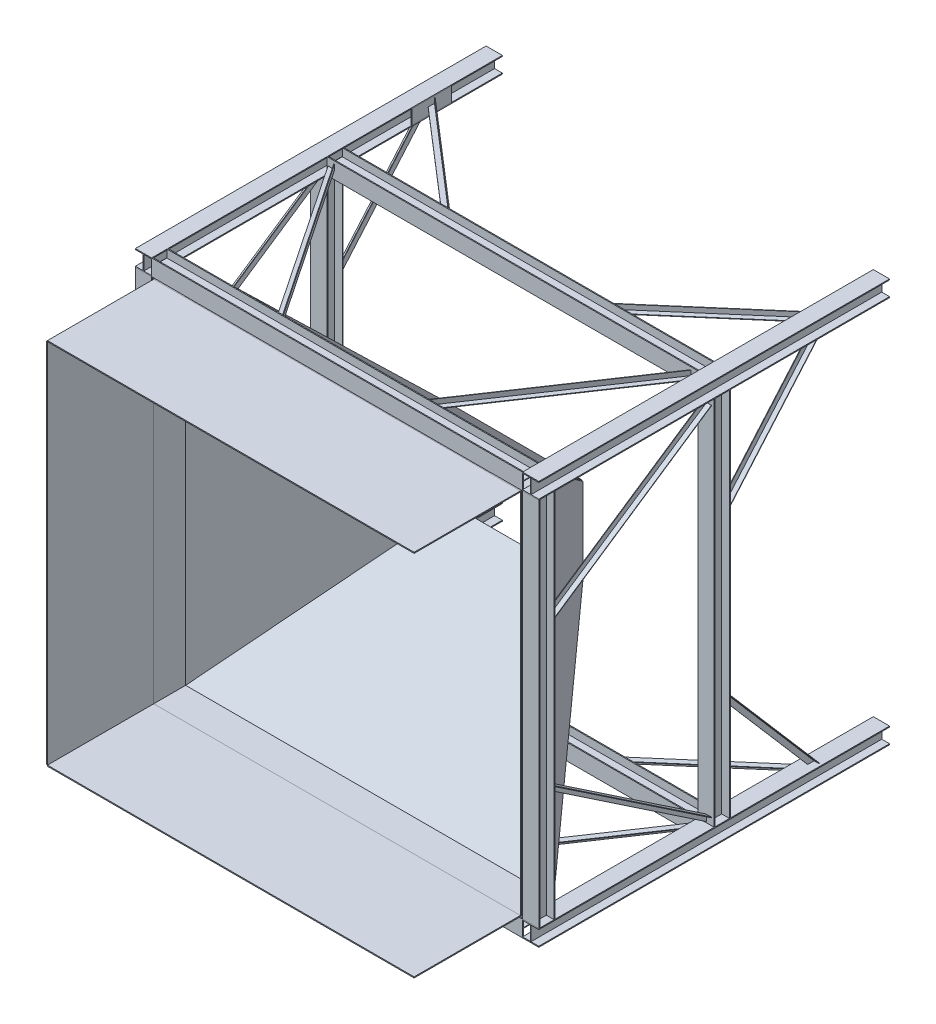
SolidWorks part; units mm, degrees
other "DetailItem1"
other "DetailItem2"
other "DetailItem3"
other "DetailItem4"
other "DetailItem5"
other "DetailItem6"
other "DetailItem7"
other "DetailItem8"
other "DetailItem9"
other "DetailItem10"
other "DetailItem11"
other "DetailItem12"
other "DetailItem13"
other "DetailItem14"
other "DetailItem15"
other "DetailItem16"
other "DetailItem17"
other "DetailItem18"
other "DetailItem19"
other "DetailItem20"
other "DetailItem21"
other "DetailItem22"
other "DetailItem23"
other "DetailItem24"
other "DetailItem25"
other "DetailItem26"
other "DetailItem27"
other "DetailItem28"
other "DetailItem29"
other "DetailItem30"
other "DetailItem31"
other "DetailItem32"
other "DetailItem33"
other "DetailItem34"
other "DetailItem35"
other "DetailItem36"
other "DetailItem37"
other "DetailItem38"
other "DetailItem39"
other "DetailItem40"
other "DetailItem41"
other "DetailItem42"
other "DetailItem43"
other "DetailItem44"
other "DetailItem45"
other "DetailItem46"
other "DetailItem47"
other "DetailItem48"
other "DetailItem49"
other "DetailItem50"
other "DetailItem51"
other "DetailItem52"
other "DetailItem53"
other "DetailItem54"
other "DetailItem55"
other "DetailItem56"
other "DetailItem57"
other "DetailItem58"
other "DetailItem59"
other "DetailItem60"
other "DetailItem61"
other "DetailItem62"
other "DetailItem63"
other "DetailItem64"
other "DetailItem65"
other "DetailItem66"
other "DetailItem67"
other "DetailItem68"
other "DetailItem69"
other "DetailItem70"
other "DetailItem71"
other "DetailItem72"
other "DetailItem73"
other "Carpeta de soldadura"
other "Cordón de soldadura1"
other "Soldadura Viga H carga 1650 B"
other "Soldadura Viga H carga 3300 A"
other "Soldadura Viga H carga 3300 B"
other "Soldadura asiento a tolva carga"
other "Soldadura asiento a bastidor carga"
other "Soldadura Viga H fondo 1650 A"
other "Soldadura Viga H fondo 1650 B"
other "Soldadura Viga H fondo 3300 A"
other "Soldadura Viga H fondo 3300 B"
other "Soldadura asiento a tolva fondo"
other "Soldadura asiento a bastidor fondo"
other "Soldadura Viga H izquierda 1650 A"
other "Soldadura Viga H izquierda 1650 B"
other "Soldadura Viga H izquierda 3300 A"
other "Soldadura Viga H izquierda 3300 B"
other "Soldadura asiento a tolva izquierda"
other "Soldadura asiento a bastidor izquierda"
other "Soldadura Viga H derecha 1650 A"
other "Soldadura Viga H derecha 1650 B"
other "Soldadura Viga H derecha 3300 A"
other "Soldadura Viga H derecha 3300 B"
other "Soldadura asiento a tolva derecha"
other "Soldadura asiento a bastidor derecha"
other "Soldadura Angular superior carga A inferior"
other "Soldadura Angular superior carga A superior"
other "Soldadura Angular inferior carga A inferior"
other "Soldadura Angular inferior carga A superior"
other "Soldadura Angular superior carga B inferior"
other "Soldadura Angular superior carga B superior"
other "Soldadura Angular inferior carga B inferior"
other "Soldadura Angular inferior carga B superior"
other "Soldadura Angular superior fondo A inferior"
other "Soldadura Angular superior fondo A superior"
other "Soldadura Angular inferior fondo A inferior"
other "Soldadura Angular inferior fondo A superior"
other "Soldadura Angular superior fondo B inferior"
other "Soldadura Angular superior fondo B superior"
other "Soldadura Angular inferior fondo B inferior"
other "Soldadura Angular inferior fondo B superior"
other "Soldadura Angular superior izquierda A inferior"
other "Soldadura Angular superior izquierda A superior"
other "Soldadura Angular inferior izquierda A inferior"
other "Soldadura Angular inferior izquierda A superior"
other "Soldadura Angular superior izquierda B inferior"
other "Soldadura Angular superior izquierda B superior"
other "Soldadura Angular inferior izquierda B inferior"
other "Soldadura Angular inferior izquierda B superior"
other "Soldadura Angular superior derecha A inferior"
other "Soldadura Angular superior derecha A superior"
other "Soldadura Angular inferior derecha A inferior"
other "Soldadura Angular inferior derecha A superior"
other "Soldadura Angular superior derecha B inferior"
other "Soldadura Angular superior derecha B superior"
other "Soldadura Angular inferior derecha B inferior"
other "Soldadura Angular inferior derecha B superior"
other "Soldadura alerón a collar lateral Y negativo"
other "Soldadura esquina del collar lateral Y negativo"
other "Soldadura quiebre del embudo lateral Y negativo"
other "Soldadura arista inclinada lateral Y negativo"
other "Soldadura esquina del collar carga"
other "Soldadura quiebre del embudo carga"
other "Soldadura arista inclinada carga"
other "Soldadura alerón a collar lateral Y positivo"
other "Soldadura esquina del collar lateral Y positivo"
other "Soldadura quiebre del embudo lateral Y positivo"
other "Soldadura arista inclinada lateral Y positivo"
other "Soldadura alerón a collar fondo X negativo"
other "Soldadura esquina del collar fondo X negativo"
other "Soldadura quiebre del embudo fondo X negativo"
other "Soldadura arista inclinada fondo X negativo"
other "Soldadura esquina alerones fondo Y positivo"
other "Soldadura esquina alerones fondo Y negativo"
material "ASTM A36 Steel"
ref_plane "Front Plane" through (0, 0, 0) normal (0, 0, 1) x (1, 0, 0)
ref_plane "Top Plane" through (0, 0, 0) normal (0, 1, 0) x (1, 0, 0)
ref_plane "Right Plane" through (0, 0, 0) normal (1, 0, 0) x (0, 0, -1)
sketch3d "Referencias 1"
  point P0 (0, 0, 0)
  point P1 (0, -190, 0)
  point P2 (200, 0, 0)
ref_plane "Plano de perfil 1 estructura" through (0, 0, 0) normal (0, 0, 1) x (1, 0, 0)
sketch "Contorno Columna H 1" plane through (0, 0, 0) normal (0, 0, 1) x (1, 0, 0)
  line L0 (-1898, -1898) -> (-1745, -1898)
  line L1 (-1745, -1898) -> (-1745, -1889)
  line L2 (-1745, -1889) -> (-1818.25, -1889)
  line L3 (-1818.25, -1889) -> (-1818.25, -1754)
  line L4 (-1818.25, -1754) -> (-1745, -1754)
  line L5 (-1745, -1754) -> (-1745, -1745)
  line L6 (-1745, -1745) -> (-1898, -1745)
  line L7 (-1898, -1745) -> (-1898, -1754)
  line L8 (-1898, -1754) -> (-1824.75, -1754)
  line L9 (-1824.75, -1754) -> (-1824.75, -1889)
  line L10 (-1824.75, -1889) -> (-1898, -1889)
  line L11 (-1898, -1889) -> (-1898, -1898)
extrude "Columna H 1" add sketch "Contorno Columna H 1" along normal blind 3300 separate body
sketch "Contorno Columna H 2" plane through (0, 0, 0) normal (0, 0, 1) x (1, 0, 0)
  line L0 (-1898, 1745) -> (-1745, 1745)
  line L1 (-1745, 1745) -> (-1745, 1754)
  line L2 (-1745, 1754) -> (-1818.25, 1754)
  line L3 (-1818.25, 1754) -> (-1818.25, 1889)
  line L4 (-1818.25, 1889) -> (-1745, 1889)
  line L5 (-1745, 1889) -> (-1745, 1898)
  line L6 (-1745, 1898) -> (-1898, 1898)
  line L7 (-1898, 1898) -> (-1898, 1889)
  line L8 (-1898, 1889) -> (-1824.75, 1889)
  line L9 (-1824.75, 1889) -> (-1824.75, 1754)
  line L10 (-1824.75, 1754) -> (-1898, 1754)
  line L11 (-1898, 1754) -> (-1898, 1745)
extrude "Columna H 2" add sketch "Contorno Columna H 2" along normal blind 3300 separate body
sketch "Contorno Columna H 3" plane through (0, 0, 0) normal (0, 0, 1) x (1, 0, 0)
  line L0 (1745, -1898) -> (1898, -1898)
  line L1 (1898, -1898) -> (1898, -1889)
  line L2 (1898, -1889) -> (1824.75, -1889)
  line L3 (1824.75, -1889) -> (1824.75, -1754)
  line L4 (1824.75, -1754) -> (1898, -1754)
  line L5 (1898, -1754) -> (1898, -1745)
  line L6 (1898, -1745) -> (1745, -1745)
  line L7 (1745, -1745) -> (1745, -1754)
  line L8 (1745, -1754) -> (1818.25, -1754)
  line L9 (1818.25, -1754) -> (1818.25, -1889)
  line L10 (1818.25, -1889) -> (1745, -1889)
  line L11 (1745, -1889) -> (1745, -1898)
extrude "Columna H 3" add sketch "Contorno Columna H 3" along normal blind 3300 separate body
sketch "Contorno Columna H 4" plane through (0, 0, 0) normal (0, 0, 1) x (1, 0, 0)
  line L0 (1745, 1745) -> (1898, 1745)
  line L1 (1898, 1745) -> (1898, 1754)
  line L2 (1898, 1754) -> (1824.75, 1754)
  line L3 (1824.75, 1754) -> (1824.75, 1889)
  line L4 (1824.75, 1889) -> (1898, 1889)
  line L5 (1898, 1889) -> (1898, 1898)
  line L6 (1898, 1898) -> (1745, 1898)
  line L7 (1745, 1898) -> (1745, 1889)
  line L8 (1745, 1889) -> (1818.25, 1889)
  line L9 (1818.25, 1889) -> (1818.25, 1754)
  line L10 (1818.25, 1754) -> (1745, 1754)
  line L11 (1745, 1754) -> (1745, 1745)
extrude "Columna H 4" add sketch "Contorno Columna H 4" along normal blind 3300 separate body
sketch3d "Referencias 2"
  point P0 (-1745, 0, 0)
  point P1 (-1745, 190, 0)
  point P2 (-1745, 0, 200)
ref_plane "Plano de perfil 2 estructura" through (-1745, 0, 0) normal (1, 0, 0) x (0, 0, -1)
sketch "Contorno Viga H carga 1650" plane through (-1745, 0, 0) normal (1, 0, 0) x (0, 0, -1)
  line L0 (-1497, -1745) -> (-1497, -1898)
  line L1 (-1497, -1898) -> (-1506, -1898)
  line L2 (-1506, -1898) -> (-1506, -1824.75)
  line L3 (-1506, -1824.75) -> (-1641, -1824.75)
  line L4 (-1641, -1824.75) -> (-1641, -1898)
  line L5 (-1641, -1898) -> (-1650, -1898)
  line L6 (-1650, -1898) -> (-1650, -1745)
  line L7 (-1650, -1745) -> (-1641, -1745)
  line L8 (-1641, -1745) -> (-1641, -1818.25)
  line L9 (-1641, -1818.25) -> (-1506, -1818.25)
  line L10 (-1506, -1818.25) -> (-1506, -1745)
  line L11 (-1506, -1745) -> (-1497, -1745)
extrude "Viga H carga 1650" add sketch "Contorno Viga H carga 1650" along normal blind 3490 separate body
sketch "Contorno Viga H carga 3300" plane through (-1745, 0, 0) normal (1, 0, 0) x (0, 0, -1)
  line L0 (-3147, -1745) -> (-3147, -1898)
  line L1 (-3147, -1898) -> (-3156, -1898)
  line L2 (-3156, -1898) -> (-3156, -1824.75)
  line L3 (-3156, -1824.75) -> (-3291, -1824.75)
  line L4 (-3291, -1824.75) -> (-3291, -1898)
  line L5 (-3291, -1898) -> (-3300, -1898)
  line L6 (-3300, -1898) -> (-3300, -1745)
  line L7 (-3300, -1745) -> (-3291, -1745)
  line L8 (-3291, -1745) -> (-3291, -1818.25)
  line L9 (-3291, -1818.25) -> (-3156, -1818.25)
  line L10 (-3156, -1818.25) -> (-3156, -1745)
  line L11 (-3156, -1745) -> (-3147, -1745)
extrude "Viga H carga 3300" add sketch "Contorno Viga H carga 3300" along normal blind 3490 separate body
sketch "Contorno Cierre columna carga A" plane through (-1745, 0, 0) normal (1, 0, 0) x (0, 0, -1)
  line L0 (-480, -1754) -> (-480, -1889)
  line L1 (-480, -1889) -> (-850, -1889)
  line L2 (-850, -1889) -> (-850, -1754)
  line L3 (-850, -1754) -> (-480, -1754)
extrude "Cierre columna carga A" add sketch "Contorno Cierre columna carga A" against normal blind 8 separate body
sketch3d "Referencias 3"
  point P0 (0, -1821.5, 0)
  point P1 (-190, -1821.5, 0)
  point P2 (0, -1821.5, 200)
ref_plane "Plano de perfil 3 estructura" through (0, -1821.5, 0) normal (0, 1, 0) x (1, 0, 0)
sketch "Contorno Ala plana Angular superior carga A" plane through (0, -1821.5, 0) normal (0, 1, 0) x (1, 0, 0)
  line L0 (-1674.8701, -1650) -> (-1735.1299, -1650)
  line L1 (-1735.1299, -1650) -> (-728.1299, -3147)
  line L2 (-728.1299, -3147) -> (-667.8701, -3147)
  line L3 (-667.8701, -3147) -> (-1674.8701, -1650)
extrude "Ala plana Angular superior carga A" add sketch "Contorno Ala plana Angular superior carga A" against normal blind 5 separate body
sketch3d "Referencias 4"
  point P0 (0, -1826.5, 0)
  point P1 (-190, -1826.5, 0)
  point P2 (0, -1826.5, 200)
ref_plane "Plano de perfil 4 estructura" through (0, -1826.5, 0) normal (0, 1, 0) x (1, 0, 0)
sketch "Contorno Retorno Angular superior carga A" plane through (0, -1826.5, 0) normal (0, 1, 0) x (1, 0, 0)
  line L0 (-1674.8701, -1650) -> (-1680.8961, -1650)
  line L1 (-1680.8961, -1650) -> (-673.8961, -3147)
  line L2 (-673.8961, -3147) -> (-667.8701, -3147)
  line L3 (-667.8701, -3147) -> (-1674.8701, -1650)
extrude "Retorno Angular superior carga A" add sketch "Contorno Retorno Angular superior carga A" against normal blind 45 separate body
combine bodies "Angular superior carga A" operation type add bodies to combine 108 109
sketch "Contorno Ala plana Angular inferior carga A" plane through (0, -1821.5, 0) normal (0, 1, 0) x (1, 0, 0)
  line L0 (-1745, -631.991) -> (-1745, -698.009)
  line L1 (-1745, -698.009) -> (-818.2856, -1497)
  line L2 (-818.2856, -1497) -> (-741.7144, -1497)
  line L3 (-741.7144, -1497) -> (-1745, -631.991)
extrude "Ala plana Angular inferior carga A" add sketch "Contorno Ala plana Angular inferior carga A" against normal blind 5 separate body
sketch "Contorno Retorno Angular inferior carga A" plane through (0, -1826.5, 0) normal (0, 1, 0) x (1, 0, 0)
  line L0 (-1745, -631.991) -> (-1745, -638.5928)
  line L1 (-1745, -638.5928) -> (-749.3715, -1497)
  line L2 (-749.3715, -1497) -> (-741.7144, -1497)
  line L3 (-741.7144, -1497) -> (-1745, -631.991)
extrude "Retorno Angular inferior carga A" add sketch "Contorno Retorno Angular inferior carga A" against normal blind 45 separate body
combine bodies "Angular inferior carga A" operation type add bodies to combine 111 112
sketch3d "Referencias 5"
  point P0 (1745, 0, 0)
  point P1 (1745, 190, 0)
  point P2 (1745, 0, 200)
ref_plane "Plano de perfil 5 estructura" through (1745, 0, 0) normal (1, 0, 0) x (0, 0, -1)
sketch "Contorno Cierre columna carga B" plane through (1745, 0, 0) normal (1, 0, 0) x (0, 0, -1)
  line L0 (-480, -1754) -> (-480, -1889)
  line L1 (-480, -1889) -> (-850, -1889)
  line L2 (-850, -1889) -> (-850, -1754)
  line L3 (-850, -1754) -> (-480, -1754)
extrude "Cierre columna carga B" add sketch "Contorno Cierre columna carga B" along normal blind 8 separate body
sketch "Contorno Ala plana Angular superior carga B" plane through (0, -1821.5, 0) normal (0, 1, 0) x (1, 0, 0)
  line L0 (1674.8701, -1650) -> (1735.1299, -1650)
  line L1 (1735.1299, -1650) -> (728.1299, -3147)
  line L2 (728.1299, -3147) -> (667.8701, -3147)
  line L3 (667.8701, -3147) -> (1674.8701, -1650)
extrude "Ala plana Angular superior carga B" add sketch "Contorno Ala plana Angular superior carga B" against normal blind 5 separate body
sketch "Contorno Retorno Angular superior carga B" plane through (0, -1826.5, 0) normal (0, 1, 0) x (1, 0, 0)
  line L0 (1674.8701, -1650) -> (1680.8961, -1650)
  line L1 (1680.8961, -1650) -> (673.8961, -3147)
  line L2 (673.8961, -3147) -> (667.8701, -3147)
  line L3 (667.8701, -3147) -> (1674.8701, -1650)
extrude "Retorno Angular superior carga B" add sketch "Contorno Retorno Angular superior carga B" against normal blind 45 separate body
combine bodies "Angular superior carga B" operation type add bodies to combine 115 116
sketch "Contorno Ala plana Angular inferior carga B" plane through (0, -1821.5, 0) normal (0, 1, 0) x (1, 0, 0)
  line L0 (1745, -631.991) -> (1745, -698.009)
  line L1 (1745, -698.009) -> (818.2856, -1497)
  line L2 (818.2856, -1497) -> (741.7144, -1497)
  line L3 (741.7144, -1497) -> (1745, -631.991)
extrude "Ala plana Angular inferior carga B" add sketch "Contorno Ala plana Angular inferior carga B" against normal blind 5 separate body
sketch "Contorno Retorno Angular inferior carga B" plane through (0, -1826.5, 0) normal (0, 1, 0) x (1, 0, 0)
  line L0 (1745, -631.991) -> (1745, -638.5928)
  line L1 (1745, -638.5928) -> (749.3715, -1497)
  line L2 (749.3715, -1497) -> (741.7144, -1497)
  line L3 (741.7144, -1497) -> (1745, -631.991)
extrude "Retorno Angular inferior carga B" add sketch "Contorno Retorno Angular inferior carga B" against normal blind 45 separate body
combine bodies "Angular inferior carga B" operation type add bodies to combine 118 119
sketch3d "Referencias 6"
  point P0 (0, 0, 3281.475)
  point P1 (0, -190, 3281.475)
  point P2 (200, 0, 3281.475)
ref_plane "Plano de perfil 6 estructura" through (0, 0, 3281.475) normal (0, 0, 1) x (1, 0, 0)
sketch "Contorno Asiento soldado carga" plane through (0, 0, 3281.475) normal (0, 0, 1) x (1, 0, 0)
  line L0 (-1450, -1734.525) -> (1450, -1734.525)
  line L1 (1450, -1734.525) -> (1450, -1818.25)
  line L2 (1450, -1818.25) -> (-1450, -1818.25)
  line L3 (-1450, -1818.25) -> (-1450, -1734.525)
extrude "Asiento soldado carga" add sketch "Contorno Asiento soldado carga" along normal blind 9.525 separate body
sketch "Contorno Viga H fondo 1650" plane through (-1745, 0, 0) normal (1, 0, 0) x (0, 0, -1)
  line L0 (-1497, 1745) -> (-1497, 1898)
  line L1 (-1497, 1898) -> (-1506, 1898)
  line L2 (-1506, 1898) -> (-1506, 1824.75)
  line L3 (-1506, 1824.75) -> (-1641, 1824.75)
  line L4 (-1641, 1824.75) -> (-1641, 1898)
  line L5 (-1641, 1898) -> (-1650, 1898)
  line L6 (-1650, 1898) -> (-1650, 1745)
  line L7 (-1650, 1745) -> (-1641, 1745)
  line L8 (-1641, 1745) -> (-1641, 1818.25)
  line L9 (-1641, 1818.25) -> (-1506, 1818.25)
  line L10 (-1506, 1818.25) -> (-1506, 1745)
  line L11 (-1506, 1745) -> (-1497, 1745)
extrude "Viga H fondo 1650" add sketch "Contorno Viga H fondo 1650" along normal blind 3490 separate body
sketch "Contorno Viga H fondo 3300" plane through (-1745, 0, 0) normal (1, 0, 0) x (0, 0, -1)
  line L0 (-3147, 1745) -> (-3147, 1898)
  line L1 (-3147, 1898) -> (-3156, 1898)
  line L2 (-3156, 1898) -> (-3156, 1824.75)
  line L3 (-3156, 1824.75) -> (-3291, 1824.75)
  line L4 (-3291, 1824.75) -> (-3291, 1898)
  line L5 (-3291, 1898) -> (-3300, 1898)
  line L6 (-3300, 1898) -> (-3300, 1745)
  line L7 (-3300, 1745) -> (-3291, 1745)
  line L8 (-3291, 1745) -> (-3291, 1818.25)
  line L9 (-3291, 1818.25) -> (-3156, 1818.25)
  line L10 (-3156, 1818.25) -> (-3156, 1745)
  line L11 (-3156, 1745) -> (-3147, 1745)
extrude "Viga H fondo 3300" add sketch "Contorno Viga H fondo 3300" along normal blind 3490 separate body
sketch "Contorno Cierre columna fondo A" plane through (-1745, 0, 0) normal (1, 0, 0) x (0, 0, -1)
  line L0 (-480, 1754) -> (-480, 1889)
  line L1 (-480, 1889) -> (-850, 1889)
  line L2 (-850, 1889) -> (-850, 1754)
  line L3 (-850, 1754) -> (-480, 1754)
extrude "Cierre columna fondo A" add sketch "Contorno Cierre columna fondo A" against normal blind 8 separate body
sketch3d "Referencias 7"
  point P0 (0, 1821.5, 0)
  point P1 (-190, 1821.5, 0)
  point P2 (0, 1821.5, 200)
ref_plane "Plano de perfil 7 estructura" through (0, 1821.5, 0) normal (0, 1, 0) x (1, 0, 0)
sketch "Contorno Ala plana Angular superior fondo A" plane through (0, 1821.5, 0) normal (0, 1, 0) x (1, 0, 0)
  line L0 (-1674.8701, -1650) -> (-1735.1299, -1650)
  line L1 (-1735.1299, -1650) -> (-728.1299, -3147)
  line L2 (-728.1299, -3147) -> (-667.8701, -3147)
  line L3 (-667.8701, -3147) -> (-1674.8701, -1650)
extrude "Ala plana Angular superior fondo A" add sketch "Contorno Ala plana Angular superior fondo A" along normal blind 5 separate body
sketch3d "Referencias 8"
  point P0 (0, 1826.5, 0)
  point P1 (-190, 1826.5, 0)
  point P2 (0, 1826.5, 200)
ref_plane "Plano de perfil 8 estructura" through (0, 1826.5, 0) normal (0, 1, 0) x (1, 0, 0)
sketch "Contorno Retorno Angular superior fondo A" plane through (0, 1826.5, 0) normal (0, 1, 0) x (1, 0, 0)
  line L0 (-1674.8701, -1650) -> (-1680.8961, -1650)
  line L1 (-1680.8961, -1650) -> (-673.8961, -3147)
  line L2 (-673.8961, -3147) -> (-667.8701, -3147)
  line L3 (-667.8701, -3147) -> (-1674.8701, -1650)
extrude "Retorno Angular superior fondo A" add sketch "Contorno Retorno Angular superior fondo A" along normal blind 45 separate body
combine bodies "Angular superior fondo A" operation type add bodies to combine 125 126
sketch "Contorno Ala plana Angular inferior fondo A" plane through (0, 1821.5, 0) normal (0, 1, 0) x (1, 0, 0)
  line L0 (-1745, -631.991) -> (-1745, -698.009)
  line L1 (-1745, -698.009) -> (-818.2856, -1497)
  line L2 (-818.2856, -1497) -> (-741.7144, -1497)
  line L3 (-741.7144, -1497) -> (-1745, -631.991)
extrude "Ala plana Angular inferior fondo A" add sketch "Contorno Ala plana Angular inferior fondo A" along normal blind 5 separate body
sketch "Contorno Retorno Angular inferior fondo A" plane through (0, 1826.5, 0) normal (0, 1, 0) x (1, 0, 0)
  line L0 (-1745, -631.991) -> (-1745, -638.5928)
  line L1 (-1745, -638.5928) -> (-749.3715, -1497)
  line L2 (-749.3715, -1497) -> (-741.7144, -1497)
  line L3 (-741.7144, -1497) -> (-1745, -631.991)
extrude "Retorno Angular inferior fondo A" add sketch "Contorno Retorno Angular inferior fondo A" along normal blind 45 separate body
combine bodies "Angular inferior fondo A" operation type add bodies to combine 128 129
sketch "Contorno Cierre columna fondo B" plane through (1745, 0, 0) normal (1, 0, 0) x (0, 0, -1)
  line L0 (-480, 1754) -> (-480, 1889)
  line L1 (-480, 1889) -> (-850, 1889)
  line L2 (-850, 1889) -> (-850, 1754)
  line L3 (-850, 1754) -> (-480, 1754)
extrude "Cierre columna fondo B" add sketch "Contorno Cierre columna fondo B" along normal blind 8 separate body
sketch "Contorno Ala plana Angular superior fondo B" plane through (0, 1821.5, 0) normal (0, 1, 0) x (1, 0, 0)
  line L0 (1674.8701, -1650) -> (1735.1299, -1650)
  line L1 (1735.1299, -1650) -> (728.1299, -3147)
  line L2 (728.1299, -3147) -> (667.8701, -3147)
  line L3 (667.8701, -3147) -> (1674.8701, -1650)
extrude "Ala plana Angular superior fondo B" add sketch "Contorno Ala plana Angular superior fondo B" along normal blind 5 separate body
sketch "Contorno Retorno Angular superior fondo B" plane through (0, 1826.5, 0) normal (0, 1, 0) x (1, 0, 0)
  line L0 (1674.8701, -1650) -> (1680.8961, -1650)
  line L1 (1680.8961, -1650) -> (673.8961, -3147)
  line L2 (673.8961, -3147) -> (667.8701, -3147)
  line L3 (667.8701, -3147) -> (1674.8701, -1650)
extrude "Retorno Angular superior fondo B" add sketch "Contorno Retorno Angular superior fondo B" along normal blind 45 separate body
combine bodies "Angular superior fondo B" operation type add bodies to combine 132 133
sketch "Contorno Ala plana Angular inferior fondo B" plane through (0, 1821.5, 0) normal (0, 1, 0) x (1, 0, 0)
  line L0 (1745, -631.991) -> (1745, -698.009)
  line L1 (1745, -698.009) -> (818.2856, -1497)
  line L2 (818.2856, -1497) -> (741.7144, -1497)
  line L3 (741.7144, -1497) -> (1745, -631.991)
extrude "Ala plana Angular inferior fondo B" add sketch "Contorno Ala plana Angular inferior fondo B" along normal blind 5 separate body
sketch "Contorno Retorno Angular inferior fondo B" plane through (0, 1826.5, 0) normal (0, 1, 0) x (1, 0, 0)
  line L0 (1745, -631.991) -> (1745, -638.5928)
  line L1 (1745, -638.5928) -> (749.3715, -1497)
  line L2 (749.3715, -1497) -> (741.7144, -1497)
  line L3 (741.7144, -1497) -> (1745, -631.991)
extrude "Retorno Angular inferior fondo B" add sketch "Contorno Retorno Angular inferior fondo B" along normal blind 45 separate body
combine bodies "Angular inferior fondo B" operation type add bodies to combine 135 136
sketch "Contorno Asiento soldado fondo" plane through (0, 0, 3281.475) normal (0, 0, 1) x (1, 0, 0)
  line L0 (-1450, 1734.525) -> (1450, 1734.525)
  line L1 (1450, 1734.525) -> (1450, 1818.25)
  line L2 (1450, 1818.25) -> (-1450, 1818.25)
  line L3 (-1450, 1818.25) -> (-1450, 1734.525)
extrude "Asiento soldado fondo" add sketch "Contorno Asiento soldado fondo" along normal blind 9.525 separate body
sketch3d "Referencias 9"
  point P0 (0, -1745, 0)
  point P1 (-190, -1745, 0)
  point P2 (0, -1745, 200)
ref_plane "Plano de perfil 9 estructura" through (0, -1745, 0) normal (0, 1, 0) x (1, 0, 0)
sketch "Contorno Viga H izquierda 1650" plane through (0, -1745, 0) normal (0, 1, 0) x (1, 0, 0)
  line L0 (-1745, -1497) -> (-1898, -1497)
  line L1 (-1898, -1497) -> (-1898, -1506)
  line L2 (-1898, -1506) -> (-1824.75, -1506)
  line L3 (-1824.75, -1506) -> (-1824.75, -1641)
  line L4 (-1824.75, -1641) -> (-1898, -1641)
  line L5 (-1898, -1641) -> (-1898, -1650)
  line L6 (-1898, -1650) -> (-1745, -1650)
  line L7 (-1745, -1650) -> (-1745, -1641)
  line L8 (-1745, -1641) -> (-1818.25, -1641)
  line L9 (-1818.25, -1641) -> (-1818.25, -1506)
  line L10 (-1818.25, -1506) -> (-1745, -1506)
  line L11 (-1745, -1506) -> (-1745, -1497)
extrude "Viga H izquierda 1650" add sketch "Contorno Viga H izquierda 1650" along normal blind 3490 separate body
sketch "Contorno Viga H izquierda 3300" plane through (0, -1745, 0) normal (0, 1, 0) x (1, 0, 0)
  line L0 (-1745, -3147) -> (-1898, -3147)
  line L1 (-1898, -3147) -> (-1898, -3156)
  line L2 (-1898, -3156) -> (-1824.75, -3156)
  line L3 (-1824.75, -3156) -> (-1824.75, -3291)
  line L4 (-1824.75, -3291) -> (-1898, -3291)
  line L5 (-1898, -3291) -> (-1898, -3300)
  line L6 (-1898, -3300) -> (-1745, -3300)
  line L7 (-1745, -3300) -> (-1745, -3291)
  line L8 (-1745, -3291) -> (-1818.25, -3291)
  line L9 (-1818.25, -3291) -> (-1818.25, -3156)
  line L10 (-1818.25, -3156) -> (-1745, -3156)
  line L11 (-1745, -3156) -> (-1745, -3147)
extrude "Viga H izquierda 3300" add sketch "Contorno Viga H izquierda 3300" along normal blind 3490 separate body
sketch3d "Referencias 10"
  point P0 (-1821.5, 0, 0)
  point P1 (-1821.5, 190, 0)
  point P2 (-1821.5, 0, 200)
ref_plane "Plano de perfil 10 estructura" through (-1821.5, 0, 0) normal (1, 0, 0) x (0, 0, -1)
sketch "Contorno Ala plana Angular superior izquierda A" plane through (-1821.5, 0, 0) normal (1, 0, 0) x (0, 0, -1)
  line L0 (-1650, -1674.8701) -> (-1650, -1735.1299)
  line L1 (-1650, -1735.1299) -> (-3147, -728.1299)
  line L2 (-3147, -728.1299) -> (-3147, -667.8701)
  line L3 (-3147, -667.8701) -> (-1650, -1674.8701)
extrude "Ala plana Angular superior izquierda A" add sketch "Contorno Ala plana Angular superior izquierda A" against normal blind 5 separate body
sketch3d "Referencias 11"
  point P0 (-1826.5, 0, 0)
  point P1 (-1826.5, 190, 0)
  point P2 (-1826.5, 0, 200)
ref_plane "Plano de perfil 11 estructura" through (-1826.5, 0, 0) normal (1, 0, 0) x (0, 0, -1)
sketch "Contorno Retorno Angular superior izquierda A" plane through (-1826.5, 0, 0) normal (1, 0, 0) x (0, 0, -1)
  line L0 (-1650, -1674.8701) -> (-1650, -1680.8961)
  line L1 (-1650, -1680.8961) -> (-3147, -673.8961)
  line L2 (-3147, -673.8961) -> (-3147, -667.8701)
  line L3 (-3147, -667.8701) -> (-1650, -1674.8701)
extrude "Retorno Angular superior izquierda A" add sketch "Contorno Retorno Angular superior izquierda A" against normal blind 45 separate body
combine bodies "Angular superior izquierda A" operation type add bodies to combine 141 142
sketch "Contorno Ala plana Angular inferior izquierda A" plane through (-1821.5, 0, 0) normal (1, 0, 0) x (0, 0, -1)
  line L0 (-631.991, -1745) -> (-698.009, -1745)
  line L1 (-698.009, -1745) -> (-1497, -818.2856)
  line L2 (-1497, -818.2856) -> (-1497, -741.7144)
  line L3 (-1497, -741.7144) -> (-631.991, -1745)
extrude "Ala plana Angular inferior izquierda A" add sketch "Contorno Ala plana Angular inferior izquierda A" against normal blind 5 separate body
sketch "Contorno Retorno Angular inferior izquierda A" plane through (-1826.5, 0, 0) normal (1, 0, 0) x (0, 0, -1)
  line L0 (-631.991, -1745) -> (-638.5928, -1745)
  line L1 (-638.5928, -1745) -> (-1497, -749.3715)
  line L2 (-1497, -749.3715) -> (-1497, -741.7144)
  line L3 (-1497, -741.7144) -> (-631.991, -1745)
extrude "Retorno Angular inferior izquierda A" add sketch "Contorno Retorno Angular inferior izquierda A" against normal blind 45 separate body
combine bodies "Angular inferior izquierda A" operation type add bodies to combine 144 145
sketch "Contorno Ala plana Angular superior izquierda B" plane through (-1821.5, 0, 0) normal (1, 0, 0) x (0, 0, -1)
  line L0 (-1650, 1674.8701) -> (-1650, 1735.1299)
  line L1 (-1650, 1735.1299) -> (-3147, 728.1299)
  line L2 (-3147, 728.1299) -> (-3147, 667.8701)
  line L3 (-3147, 667.8701) -> (-1650, 1674.8701)
extrude "Ala plana Angular superior izquierda B" add sketch "Contorno Ala plana Angular superior izquierda B" against normal blind 5 separate body
sketch "Contorno Retorno Angular superior izquierda B" plane through (-1826.5, 0, 0) normal (1, 0, 0) x (0, 0, -1)
  line L0 (-1650, 1674.8701) -> (-1650, 1680.8961)
  line L1 (-1650, 1680.8961) -> (-3147, 673.8961)
  line L2 (-3147, 673.8961) -> (-3147, 667.8701)
  line L3 (-3147, 667.8701) -> (-1650, 1674.8701)
extrude "Retorno Angular superior izquierda B" add sketch "Contorno Retorno Angular superior izquierda B" against normal blind 45 separate body
combine bodies "Angular superior izquierda B" operation type add bodies to combine 147 148
sketch "Contorno Ala plana Angular inferior izquierda B" plane through (-1821.5, 0, 0) normal (1, 0, 0) x (0, 0, -1)
  line L0 (-631.991, 1745) -> (-698.009, 1745)
  line L1 (-698.009, 1745) -> (-1497, 818.2856)
  line L2 (-1497, 818.2856) -> (-1497, 741.7144)
  line L3 (-1497, 741.7144) -> (-631.991, 1745)
extrude "Ala plana Angular inferior izquierda B" add sketch "Contorno Ala plana Angular inferior izquierda B" against normal blind 5 separate body
sketch "Contorno Retorno Angular inferior izquierda B" plane through (-1826.5, 0, 0) normal (1, 0, 0) x (0, 0, -1)
  line L0 (-631.991, 1745) -> (-638.5928, 1745)
  line L1 (-638.5928, 1745) -> (-1497, 749.3715)
  line L2 (-1497, 749.3715) -> (-1497, 741.7144)
  line L3 (-1497, 741.7144) -> (-631.991, 1745)
extrude "Retorno Angular inferior izquierda B" add sketch "Contorno Retorno Angular inferior izquierda B" against normal blind 45 separate body
combine bodies "Angular inferior izquierda B" operation type add bodies to combine 150 151
sketch "Contorno Asiento soldado izquierda" plane through (0, 0, 3281.475) normal (0, 0, 1) x (1, 0, 0)
  line L0 (-1734.525, -1450) -> (-1734.525, 1450)
  line L1 (-1734.525, 1450) -> (-1818.25, 1450)
  line L2 (-1818.25, 1450) -> (-1818.25, -1450)
  line L3 (-1818.25, -1450) -> (-1734.525, -1450)
extrude "Asiento soldado izquierda" add sketch "Contorno Asiento soldado izquierda" along normal blind 9.525 separate body
sketch "Contorno Viga H derecha 1650" plane through (0, -1745, 0) normal (0, 1, 0) x (1, 0, 0)
  line L0 (1745, -1497) -> (1898, -1497)
  line L1 (1898, -1497) -> (1898, -1506)
  line L2 (1898, -1506) -> (1824.75, -1506)
  line L3 (1824.75, -1506) -> (1824.75, -1641)
  line L4 (1824.75, -1641) -> (1898, -1641)
  line L5 (1898, -1641) -> (1898, -1650)
  line L6 (1898, -1650) -> (1745, -1650)
  line L7 (1745, -1650) -> (1745, -1641)
  line L8 (1745, -1641) -> (1818.25, -1641)
  line L9 (1818.25, -1641) -> (1818.25, -1506)
  line L10 (1818.25, -1506) -> (1745, -1506)
  line L11 (1745, -1506) -> (1745, -1497)
extrude "Viga H derecha 1650" add sketch "Contorno Viga H derecha 1650" along normal blind 3490 separate body
sketch "Contorno Viga H derecha 3300" plane through (0, -1745, 0) normal (0, 1, 0) x (1, 0, 0)
  line L0 (1745, -3147) -> (1898, -3147)
  line L1 (1898, -3147) -> (1898, -3156)
  line L2 (1898, -3156) -> (1824.75, -3156)
  line L3 (1824.75, -3156) -> (1824.75, -3291)
  line L4 (1824.75, -3291) -> (1898, -3291)
  line L5 (1898, -3291) -> (1898, -3300)
  line L6 (1898, -3300) -> (1745, -3300)
  line L7 (1745, -3300) -> (1745, -3291)
  line L8 (1745, -3291) -> (1818.25, -3291)
  line L9 (1818.25, -3291) -> (1818.25, -3156)
  line L10 (1818.25, -3156) -> (1745, -3156)
  line L11 (1745, -3156) -> (1745, -3147)
extrude "Viga H derecha 3300" add sketch "Contorno Viga H derecha 3300" along normal blind 3490 separate body
sketch3d "Referencias 12"
  point P0 (1821.5, 0, 0)
  point P1 (1821.5, 190, 0)
  point P2 (1821.5, 0, 200)
ref_plane "Plano de perfil 12 estructura" through (1821.5, 0, 0) normal (1, 0, 0) x (0, 0, -1)
sketch "Contorno Ala plana Angular superior derecha A" plane through (1821.5, 0, 0) normal (1, 0, 0) x (0, 0, -1)
  line L0 (-1650, -1674.8701) -> (-1650, -1735.1299)
  line L1 (-1650, -1735.1299) -> (-3147, -728.1299)
  line L2 (-3147, -728.1299) -> (-3147, -667.8701)
  line L3 (-3147, -667.8701) -> (-1650, -1674.8701)
extrude "Ala plana Angular superior derecha A" add sketch "Contorno Ala plana Angular superior derecha A" along normal blind 5 separate body
sketch3d "Referencias 13"
  point P0 (1826.5, 0, 0)
  point P1 (1826.5, 190, 0)
  point P2 (1826.5, 0, 200)
ref_plane "Plano de perfil 13 estructura" through (1826.5, 0, 0) normal (1, 0, 0) x (0, 0, -1)
sketch "Contorno Retorno Angular superior derecha A" plane through (1826.5, 0, 0) normal (1, 0, 0) x (0, 0, -1)
  line L0 (-1650, -1674.8701) -> (-1650, -1680.8961)
  line L1 (-1650, -1680.8961) -> (-3147, -673.8961)
  line L2 (-3147, -673.8961) -> (-3147, -667.8701)
  line L3 (-3147, -667.8701) -> (-1650, -1674.8701)
extrude "Retorno Angular superior derecha A" add sketch "Contorno Retorno Angular superior derecha A" along normal blind 45 separate body
combine bodies "Angular superior derecha A" operation type add bodies to combine 156 157
sketch "Contorno Ala plana Angular inferior derecha A" plane through (1821.5, 0, 0) normal (1, 0, 0) x (0, 0, -1)
  line L0 (-631.991, -1745) -> (-698.009, -1745)
  line L1 (-698.009, -1745) -> (-1497, -818.2856)
  line L2 (-1497, -818.2856) -> (-1497, -741.7144)
  line L3 (-1497, -741.7144) -> (-631.991, -1745)
extrude "Ala plana Angular inferior derecha A" add sketch "Contorno Ala plana Angular inferior derecha A" along normal blind 5 separate body
sketch "Contorno Retorno Angular inferior derecha A" plane through (1826.5, 0, 0) normal (1, 0, 0) x (0, 0, -1)
  line L0 (-631.991, -1745) -> (-638.5928, -1745)
  line L1 (-638.5928, -1745) -> (-1497, -749.3715)
  line L2 (-1497, -749.3715) -> (-1497, -741.7144)
  line L3 (-1497, -741.7144) -> (-631.991, -1745)
extrude "Retorno Angular inferior derecha A" add sketch "Contorno Retorno Angular inferior derecha A" along normal blind 45 separate body
combine bodies "Angular inferior derecha A" operation type add bodies to combine 159 160
sketch "Contorno Ala plana Angular superior derecha B" plane through (1821.5, 0, 0) normal (1, 0, 0) x (0, 0, -1)
  line L0 (-1650, 1674.8701) -> (-1650, 1735.1299)
  line L1 (-1650, 1735.1299) -> (-3147, 728.1299)
  line L2 (-3147, 728.1299) -> (-3147, 667.8701)
  line L3 (-3147, 667.8701) -> (-1650, 1674.8701)
extrude "Ala plana Angular superior derecha B" add sketch "Contorno Ala plana Angular superior derecha B" along normal blind 5 separate body
sketch "Contorno Retorno Angular superior derecha B" plane through (1826.5, 0, 0) normal (1, 0, 0) x (0, 0, -1)
  line L0 (-1650, 1674.8701) -> (-1650, 1680.8961)
  line L1 (-1650, 1680.8961) -> (-3147, 673.8961)
  line L2 (-3147, 673.8961) -> (-3147, 667.8701)
  line L3 (-3147, 667.8701) -> (-1650, 1674.8701)
extrude "Retorno Angular superior derecha B" add sketch "Contorno Retorno Angular superior derecha B" along normal blind 45 separate body
combine bodies "Angular superior derecha B" operation type add bodies to combine 162 163
sketch "Contorno Ala plana Angular inferior derecha B" plane through (1821.5, 0, 0) normal (1, 0, 0) x (0, 0, -1)
  line L0 (-631.991, 1745) -> (-698.009, 1745)
  line L1 (-698.009, 1745) -> (-1497, 818.2856)
  line L2 (-1497, 818.2856) -> (-1497, 741.7144)
  line L3 (-1497, 741.7144) -> (-631.991, 1745)
extrude "Ala plana Angular inferior derecha B" add sketch "Contorno Ala plana Angular inferior derecha B" along normal blind 5 separate body
sketch "Contorno Retorno Angular inferior derecha B" plane through (1826.5, 0, 0) normal (1, 0, 0) x (0, 0, -1)
  line L0 (-631.991, 1745) -> (-638.5928, 1745)
  line L1 (-638.5928, 1745) -> (-1497, 749.3715)
  line L2 (-1497, 749.3715) -> (-1497, 741.7144)
  line L3 (-1497, 741.7144) -> (-631.991, 1745)
extrude "Retorno Angular inferior derecha B" add sketch "Contorno Retorno Angular inferior derecha B" along normal blind 45 separate body
combine bodies "Angular inferior derecha B" operation type add bodies to combine 165 166
sketch "Contorno Asiento soldado derecha" plane through (0, 0, 3281.475) normal (0, 0, 1) x (1, 0, 0)
  line L0 (1734.525, -1450) -> (1734.525, 1450)
  line L1 (1734.525, 1450) -> (1818.25, 1450)
  line L2 (1818.25, 1450) -> (1818.25, -1450)
  line L3 (1818.25, -1450) -> (1734.525, -1450)
extrude "Asiento soldado derecha" add sketch "Contorno Asiento soldado derecha" along normal blind 9.525 separate body
sketch3d "Junta Viga H carga 1650 A"
  line L0 (-1745, -1745, 1650) -> (-1745, -1898, 1650)
sketch3d "Junta Viga H carga 1650 B"
  line L0 (1745, -1745, 1650) -> (1745, -1898, 1650)
sketch3d "Junta Viga H carga 3300 A"
  line L0 (-1745, -1745, 3300) -> (-1745, -1898, 3300)
sketch3d "Junta Viga H carga 3300 B"
  line L0 (1745, -1745, 3300) -> (1745, -1898, 3300)
sketch3d "Junta Angular superior carga A inferior"
  line L0 (-1674.8701, -1821.5, 1650) -> (-1735.1299, -1821.5, 1650)
sketch3d "Junta Angular superior carga A superior"
  line L0 (-667.8701, -1821.5, 3147) -> (-728.1299, -1821.5, 3147)
sketch3d "Junta Angular inferior carga A inferior"
  line L0 (-1745, -1821.5, 631.991) -> (-1745, -1821.5, 698.009)
sketch3d "Junta Angular inferior carga A superior"
  line L0 (-741.7144, -1821.5, 1497) -> (-818.2856, -1821.5, 1497)
sketch3d "Junta Angular superior carga B inferior"
  line L0 (1674.8701, -1821.5, 1650) -> (1735.1299, -1821.5, 1650)
sketch3d "Junta Angular superior carga B superior"
  line L0 (667.8701, -1821.5, 3147) -> (728.1299, -1821.5, 3147)
sketch3d "Junta Angular inferior carga B inferior"
  line L0 (1745, -1821.5, 631.991) -> (1745, -1821.5, 698.009)
sketch3d "Junta Angular inferior carga B superior"
  line L0 (741.7144, -1821.5, 1497) -> (818.2856, -1821.5, 1497)
sketch3d "Junta asiento a tolva carga"
  line L0 (-1450, -1734.525, 3281.475) -> (1450, -1734.525, 3281.475)
sketch3d "Junta asiento a bastidor carga"
  line L0 (-1450, -1745, 3291) -> (1450, -1745, 3291)
sketch3d "Junta Viga H fondo 1650 A"
  line L0 (-1745, 1745, 1650) -> (-1745, 1898, 1650)
sketch3d "Junta Viga H fondo 1650 B"
  line L0 (1745, 1745, 1650) -> (1745, 1898, 1650)
sketch3d "Junta Viga H fondo 3300 A"
  line L0 (-1745, 1745, 3300) -> (-1745, 1898, 3300)
sketch3d "Junta Viga H fondo 3300 B"
  line L0 (1745, 1745, 3300) -> (1745, 1898, 3300)
sketch3d "Junta Angular superior fondo A inferior"
  line L0 (-1674.8701, 1821.5, 1650) -> (-1735.1299, 1821.5, 1650)
sketch3d "Junta Angular superior fondo A superior"
  line L0 (-667.8701, 1821.5, 3147) -> (-728.1299, 1821.5, 3147)
sketch3d "Junta Angular inferior fondo A inferior"
  line L0 (-1745, 1821.5, 631.991) -> (-1745, 1821.5, 698.009)
sketch3d "Junta Angular inferior fondo A superior"
  line L0 (-741.7144, 1821.5, 1497) -> (-818.2856, 1821.5, 1497)
sketch3d "Junta Angular superior fondo B inferior"
  line L0 (1674.8701, 1821.5, 1650) -> (1735.1299, 1821.5, 1650)
sketch3d "Junta Angular superior fondo B superior"
  line L0 (667.8701, 1821.5, 3147) -> (728.1299, 1821.5, 3147)
sketch3d "Junta Angular inferior fondo B inferior"
  line L0 (1745, 1821.5, 631.991) -> (1745, 1821.5, 698.009)
sketch3d "Junta Angular inferior fondo B superior"
  line L0 (741.7144, 1821.5, 1497) -> (818.2856, 1821.5, 1497)
sketch3d "Junta asiento a tolva fondo"
  line L0 (-1450, 1734.525, 3281.475) -> (1450, 1734.525, 3281.475)
sketch3d "Junta asiento a bastidor fondo"
  line L0 (-1450, 1745, 3291) -> (1450, 1745, 3291)
sketch3d "Junta Viga H izquierda 1650 A"
  line L0 (-1745, -1745, 1650) -> (-1898, -1745, 1650)
sketch3d "Junta Viga H izquierda 1650 B"
  line L0 (-1745, 1745, 1650) -> (-1898, 1745, 1650)
sketch3d "Junta Viga H izquierda 3300 A"
  line L0 (-1745, -1745, 3300) -> (-1898, -1745, 3300)
sketch3d "Junta Viga H izquierda 3300 B"
  line L0 (-1745, 1745, 3300) -> (-1898, 1745, 3300)
sketch3d "Junta Angular superior izquierda A inferior"
  line L0 (-1821.5, -1674.8701, 1650) -> (-1821.5, -1735.1299, 1650)
sketch3d "Junta Angular superior izquierda A superior"
  line L0 (-1821.5, -667.8701, 3147) -> (-1821.5, -728.1299, 3147)
sketch3d "Junta Angular inferior izquierda A inferior"
  line L0 (-1821.5, -1745, 631.991) -> (-1821.5, -1745, 698.009)
sketch3d "Junta Angular inferior izquierda A superior"
  line L0 (-1821.5, -741.7144, 1497) -> (-1821.5, -818.2856, 1497)
sketch3d "Junta Angular superior izquierda B inferior"
  line L0 (-1821.5, 1674.8701, 1650) -> (-1821.5, 1735.1299, 1650)
sketch3d "Junta Angular superior izquierda B superior"
  line L0 (-1821.5, 667.8701, 3147) -> (-1821.5, 728.1299, 3147)
sketch3d "Junta Angular inferior izquierda B inferior"
  line L0 (-1821.5, 1745, 631.991) -> (-1821.5, 1745, 698.009)
sketch3d "Junta Angular inferior izquierda B superior"
  line L0 (-1821.5, 741.7144, 1497) -> (-1821.5, 818.2856, 1497)
sketch3d "Junta asiento a tolva izquierda"
  line L0 (-1734.525, -1450, 3281.475) -> (-1734.525, 1450, 3281.475)
sketch3d "Junta asiento a bastidor izquierda"
  line L0 (-1745, -1450, 3291) -> (-1745, 1450, 3291)
sketch3d "Junta Viga H derecha 1650 A"
  line L0 (1745, -1745, 1650) -> (1898, -1745, 1650)
sketch3d "Junta Viga H derecha 1650 B"
  line L0 (1745, 1745, 1650) -> (1898, 1745, 1650)
sketch3d "Junta Viga H derecha 3300 A"
  line L0 (1745, -1745, 3300) -> (1898, -1745, 3300)
sketch3d "Junta Viga H derecha 3300 B"
  line L0 (1745, 1745, 3300) -> (1898, 1745, 3300)
sketch3d "Junta Angular superior derecha A inferior"
  line L0 (1821.5, -1674.8701, 1650) -> (1821.5, -1735.1299, 1650)
sketch3d "Junta Angular superior derecha A superior"
  line L0 (1821.5, -667.8701, 3147) -> (1821.5, -728.1299, 3147)
sketch3d "Junta Angular inferior derecha A inferior"
  line L0 (1821.5, -1745, 631.991) -> (1821.5, -1745, 698.009)
sketch3d "Junta Angular inferior derecha A superior"
  line L0 (1821.5, -741.7144, 1497) -> (1821.5, -818.2856, 1497)
sketch3d "Junta Angular superior derecha B inferior"
  line L0 (1821.5, 1674.8701, 1650) -> (1821.5, 1735.1299, 1650)
sketch3d "Junta Angular superior derecha B superior"
  line L0 (1821.5, 667.8701, 3147) -> (1821.5, 728.1299, 3147)
sketch3d "Junta Angular inferior derecha B inferior"
  line L0 (1821.5, 1745, 631.991) -> (1821.5, 1745, 698.009)
sketch3d "Junta Angular inferior derecha B superior"
  line L0 (1821.5, 741.7144, 1497) -> (1821.5, 818.2856, 1497)
sketch3d "Junta asiento a tolva derecha"
  line L0 (1734.525, -1450, 3281.475) -> (1734.525, 1450, 3281.475)
sketch3d "Junta asiento a bastidor derecha"
  line L0 (1745, -1450, 3291) -> (1745, 1450, 3291)
sketch3d "Croquis3D1"
  point P0 (0, -1725, 0)
  point P1 (-190, -1725, 0)
  point P2 (0, -1725, 200)
ref_plane "Plano de perfil 1 tolva" through (0, -1725, 0) normal (0, 1, 0) x (1, 0, 0)
sketch "Contorno Collar lateral Y negativo" plane through (0, -1725, 0) normal (0, 1, 0) x (1, 0, 0)
  line L0 (-1725, -3300) -> (1725, -3300)
  line L1 (1725, -3300) -> (1725, -3000)
  line L2 (1725, -3000) -> (-1725, -3000)
  line L3 (-1725, -3000) -> (-1725, -3300)
extrude "Collar lateral Y negativo" add sketch "Contorno Collar lateral Y negativo" against normal blind 9.525 separate body
sketch "Contorno Alerón lateral Y negativo" plane through (0, -1725, 0) normal (0, 1, 0) x (1, 0, 0)
  line L0 (-1725, -3300) -> (1725, -3300)
  line L1 (1725, -3300) -> (1725, -4300)
  line L2 (1725, -4300) -> (-1725, -4300)
  line L3 (-1725, -4300) -> (-1725, -3300)
extrude "Alerón lateral Y negativo" add sketch "Contorno Alerón lateral Y negativo" against normal blind 9.525 separate body
sketch3d "Croquis3D2"
  point P0 (0, 587.7881, 556.2994)
  point P1 (-190, 587.7881, 556.2994)
  point P2 (0, 450.3111, 701.5581)
ref_plane "Plano de perfil 2 tolva" through (0, 587.7881, 556.2994) normal (0, 0.7263, 0.6874) x (1, 0, 0)
sketch "Contorno Embudo lateral Y negativo" plane through (0, 587.7881, 556.2994) normal (0, 0.7263, 0.6874) x (1, 0, 0)
  line L0 (-1725, -3364.619) -> (1725, -3364.619)
  line L1 (1725, -3364.619) -> (600, -1437.0234)
  line L2 (600, -1437.0234) -> (-600, -1437.0234)
  line L3 (-600, -1437.0234) -> (-1725, -3364.619)
extrude "Embudo lateral Y negativo" add sketch "Contorno Embudo lateral Y negativo" against normal blind 9.525 separate body
sketch3d "Croquis3D3"
  point P0 (1725, 0, 0)
  point P1 (1725, 190, 0)
  point P2 (1725, 0, 200)
ref_plane "Plano de perfil 3 tolva" through (1725, 0, 0) normal (1, 0, 0) x (0, 0, -1)
sketch "Contorno Collar carga" plane through (1725, 0, 0) normal (1, 0, 0) x (0, 0, -1)
  line L0 (-3300, -1725) -> (-3300, 1725)
  line L1 (-3300, 1725) -> (-3000, 1725)
  line L2 (-3000, 1725) -> (-3000, -1725)
  line L3 (-3000, -1725) -> (-3300, -1725)
extrude "Collar carga" add sketch "Contorno Collar carga" along normal blind 9.525 separate body
sketch3d "Croquis3D4"
  point P0 (-416.6634, 0, 334.8188)
  point P1 (-416.6634, 190, 334.8188)
  point P2 (-291.3852, 0, 490.7206)
ref_plane "Plano de perfil 4 tolva" through (-416.6634, 0, 334.8188) normal (0.7795, 0, -0.6264) x (-0.6264, 0, -0.7795)
sketch "Contorno Embudo carga" plane through (-416.6634, 0, 334.8188) normal (0.7795, 0, -0.6264) x (-0.6264, 0, -0.7795)
  line L0 (-3419.0515, -1725) -> (-3419.0515, 1725)
  line L1 (-3419.0515, 1725) -> (-1623.049, 400)
  line L2 (-1623.049, 400) -> (-1623.049, -400)
  line L3 (-1623.049, -400) -> (-3419.0515, -1725)
extrude "Embudo carga" add sketch "Contorno Embudo carga" along normal blind 9.525 separate body
sketch3d "Croquis3D5"
  point P0 (0, 1725, 0)
  point P1 (-190, 1725, 0)
  point P2 (0, 1725, 200)
ref_plane "Plano de perfil 5 tolva" through (0, 1725, 0) normal (0, 1, 0) x (1, 0, 0)
sketch "Contorno Collar lateral Y positivo" plane through (0, 1725, 0) normal (0, 1, 0) x (1, 0, 0)
  line L0 (1725, -3300) -> (-1725, -3300)
  line L1 (-1725, -3300) -> (-1725, -3000)
  line L2 (-1725, -3000) -> (1725, -3000)
  line L3 (1725, -3000) -> (1725, -3300)
extrude "Collar lateral Y positivo" add sketch "Contorno Collar lateral Y positivo" along normal blind 9.525 separate body
sketch "Contorno Alerón lateral Y positivo" plane through (0, 1725, 0) normal (0, 1, 0) x (1, 0, 0)
  line L0 (1725, -3300) -> (-1725, -3300)
  line L1 (-1725, -3300) -> (-1725, -4300)
  line L2 (-1725, -4300) -> (1725, -4300)
  line L3 (1725, -4300) -> (1725, -3300)
extrude "Alerón lateral Y positivo" add sketch "Contorno Alerón lateral Y positivo" along normal blind 9.525 separate body
sketch3d "Croquis3D6"
  point P0 (0, -587.7881, 556.2994)
  point P1 (-190, -587.7881, 556.2994)
  point P2 (0, -450.3111, 701.5581)
ref_plane "Plano de perfil 6 tolva" through (0, -587.7881, 556.2994) normal (0, 0.7263, -0.6874) x (1, 0, 0)
sketch "Contorno Embudo lateral Y positivo" plane through (0, -587.7881, 556.2994) normal (0, 0.7263, -0.6874) x (1, 0, 0)
  line L0 (1725, -3364.619) -> (-1725, -3364.619)
  line L1 (-1725, -3364.619) -> (-600, -1437.0234)
  line L2 (-600, -1437.0234) -> (600, -1437.0234)
  line L3 (600, -1437.0234) -> (1725, -3364.619)
extrude "Embudo lateral Y positivo" add sketch "Contorno Embudo lateral Y positivo" along normal blind 9.525 separate body
sketch3d "Croquis3D7"
  point P0 (-1725, 0, 0)
  point P1 (-1725, 190, 0)
  point P2 (-1725, 0, 200)
ref_plane "Plano de perfil 7 tolva" through (-1725, 0, 0) normal (1, 0, 0) x (0, 0, -1)
sketch "Contorno Collar fondo X negativo" plane through (-1725, 0, 0) normal (1, 0, 0) x (0, 0, -1)
  line L0 (-3300, 1725) -> (-3300, -1725)
  line L1 (-3300, -1725) -> (-3000, -1725)
  line L2 (-3000, -1725) -> (-3000, 1725)
  line L3 (-3000, 1725) -> (-3300, 1725)
extrude "Collar fondo X negativo" add sketch "Contorno Collar fondo X negativo" against normal blind 9.525 separate body
sketch "Contorno Alerón fondo X negativo" plane through (-1725, 0, 0) normal (1, 0, 0) x (0, 0, -1)
  line L0 (-3300, 1725) -> (-3300, -1725)
  line L1 (-3300, -1725) -> (-4300, -1725)
  line L2 (-4300, -1725) -> (-4300, 1725)
  line L3 (-4300, 1725) -> (-3300, 1725)
extrude "Alerón fondo X negativo" add sketch "Contorno Alerón fondo X negativo" against normal blind 9.525 separate body
sketch3d "Croquis3D8"
  point P0 (416.6634, 0, 334.8188)
  point P1 (416.6634, 190, 334.8188)
  point P2 (291.3852, 0, 490.7206)
ref_plane "Plano de perfil 8 tolva" through (416.6634, 0, 334.8188) normal (0.7795, 0, 0.6264) x (0.6264, 0, -0.7795)
sketch "Contorno Embudo fondo X negativo" plane through (416.6634, 0, 334.8188) normal (0.7795, 0, 0.6264) x (0.6264, 0, -0.7795)
  line L0 (-3419.0515, 1725) -> (-3419.0515, -1725)
  line L1 (-3419.0515, -1725) -> (-1623.049, -400)
  line L2 (-1623.049, -400) -> (-1623.049, 400)
  line L3 (-1623.049, 400) -> (-3419.0515, 1725)
extrude "Embudo fondo X negativo" add sketch "Contorno Embudo fondo X negativo" against normal blind 9.525 separate body
sketch3d "Junta alerón a collar lateral Y negativo"
  line L0 (-1725, -1725, 3300) -> (1725, -1725, 3300)
sketch3d "Junta esquina del collar lateral Y negativo"
  line L0 (-1725, -1725, 3300) -> (-1725, -1725, 3000)
sketch3d "Junta quiebre del embudo lateral Y negativo"
  line L0 (-1725, -1725, 3000) -> (1725, -1725, 3000)
sketch3d "Junta arista inclinada lateral Y negativo"
  line L0 (-1725, -1725, 3000) -> (-600, -400, 1600)
sketch3d "Junta esquina del collar carga"
  line L0 (1725, -1725, 3300) -> (1725, -1725, 3000)
sketch3d "Junta quiebre del embudo carga"
  line L0 (1725, -1725, 3000) -> (1725, 1725, 3000)
sketch3d "Junta arista inclinada carga"
  line L0 (1725, -1725, 3000) -> (600, -400, 1600)
sketch3d "Junta alerón a collar lateral Y positivo"
  line L0 (1725, 1725, 3300) -> (-1725, 1725, 3300)
sketch3d "Junta esquina del collar lateral Y positivo"
  line L0 (1725, 1725, 3300) -> (1725, 1725, 3000)
sketch3d "Junta quiebre del embudo lateral Y positivo"
  line L0 (1725, 1725, 3000) -> (-1725, 1725, 3000)
sketch3d "Junta arista inclinada lateral Y positivo"
  line L0 (1725, 1725, 3000) -> (600, 400, 1600)
sketch3d "Junta alerón a collar fondo X negativo"
  line L0 (-1725, 1725, 3300) -> (-1725, -1725, 3300)
sketch3d "Junta esquina del collar fondo X negativo"
  line L0 (-1725, 1725, 3300) -> (-1725, 1725, 3000)
sketch3d "Junta quiebre del embudo fondo X negativo"
  line L0 (-1725, 1725, 3000) -> (-1725, -1725, 3000)
sketch3d "Junta arista inclinada fondo X negativo"
  line L0 (-1725, 1725, 3000) -> (-600, 400, 1600)
sketch3d "Junta esquina alerones fondo Y positivo"
  line L0 (-1725, 1725, 3300) -> (-1725, 1725, 4300)
sketch3d "Junta esquina alerones fondo Y negativo"
  line L0 (-1725, -1725, 3300) -> (-1725, -1725, 4300)
